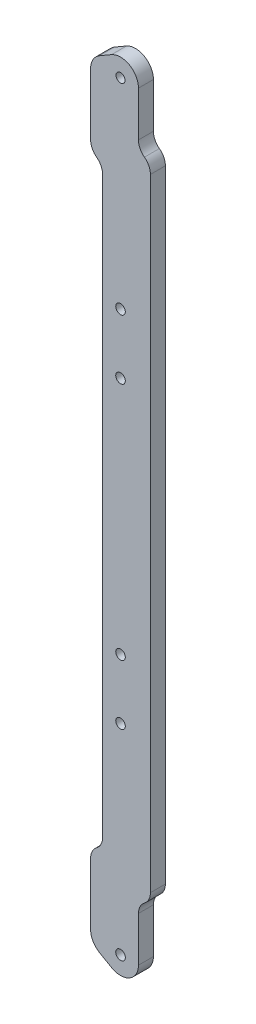
SolidWorks part; units mm, degrees
material "Thornel Mat VMA"
ref_plane "前视基准面" through (0, 0, 0) normal (0, 0, 1) x (1, 0, 0)
ref_plane "上视基准面" through (0, 0, 0) normal (0, 1, 0) x (1, 0, 0)
ref_plane "右视基准面" through (0, 0, 0) normal (1, 0, 0) x (0, 0, -1)
sketch "草图2" plane through (0, 0, 0) normal (0, 0, 1) x (1, 0, 0)
  line L1 (0, -43.1089) -> (-18, -43.1089)
  line L2 (0, -43.1089) -> (0, -133.1089)
  line L3 (0, -133.1089) -> (-18, -133.1089)
  line L4 (-18, -43.1089) -> (-18, -133.1089)
  circle A0 centre (-10, -125.1089) radius 1.6
  dimension "D1" = 18
  dimension "D2" = 8
  dimension "D3" = 3.2
  dimension "D4" = 82
  dimension "D5" = 8
extrude "凸台-拉伸1" add sketch "草图2" along normal blind 5
sketch "草图3" plane through (0, 0, 5) normal (0, 0, 1) x (1, 0, 0)
  line L0 (0, 1.8911) -> (-44.6895, 1.8911) construction
  line L1 (-18, 136.8911) -> (0, 136.8911)
  line L2 (-18, 46.8911) -> (-18, 136.8911)
  line L4 (0, -133.1089) -> (0, -43.1089)
  line L5 (0, -43.1089) -> (-18, -43.1089)
  line L6 (-18, -43.1089) -> (-18, -133.1089)
  line L7 (-18, -133.1089) -> (0, -133.1089)
  line L9 (0, -43.1089) -> (-18, -43.1089)
  line L12 (0, 136.8911) -> (0, 46.8911)
  line L15 (-18, 46.8911) -> (-18, -43.1089)
  line L16 (-18, -43.1089) -> (0, -43.1089)
  line L17 (0, 46.8911) -> (0, -43.1089)
  circle A1 centre (-10, 128.8911) radius 1.5
  line M11 (0, -43.1089) -> (-18, -43.1089)
  dimension "D3" = 8
  dimension "D4" = 10
  dimension "D5" = 127
  dimension "D2" = 45
  dimension "D1" = 0
extrude "凸台-拉伸2" add sketch "草图3" against normal blind 5 contours L0 L17 L12 L1 L2 L15 A1 | L17 L0 L15 M11 region at (-9, -20.6089, 5) region at (-8.9971, 69.2175, 5)
sketch "草图4" plane through (0, 0, 5) normal (0, 0, 1) x (1, 0, 0)
  circle A0 centre (-10, -58.1089) radius 1.6
  circle A1 centre (-10, -38.1089) radius 1.6
  circle A2 centre (-10, 41.8911) radius 1.6
  circle A3 centre (-10, 61.8911) radius 1.6
extrude "切除-拉伸1" cut sketch "草图4" against normal blind 5
sketch "草图5" plane through (0, 0, 5) normal (0, 0, 1) x (1, 0, 0)
  line L0 (-4, -125.1089) -> (-4, -110.1089)
  line L1 (0, -133.1089) -> (0, 136.8911) construction
  line L2 (-16, -125.1089) -> (-16, 128.8911)
  line L4 (0, 1.8911) -> (-11.675, 1.8911) construction
  line L5 (-16, 128.8911) -> (-16, -125.1089)
  line L6 (-4, 128.8911) -> (-4, 113.8911)
  line L7 (0, -102.1089) -> (0, -133.1089)
  line L8 (0, -133.1089) -> (-18, -133.1089)
  line L9 (-18, -133.1089) -> (-18, 136.8911)
  line L10 (-18, 136.8911) -> (0, 136.8911)
  line L11 (0, 136.8911) -> (0, 105.8911)
  circle A0 centre (-10, -125.1089) radius 6
  arc A1 (-4, -110.1089) -> (-2, -106.1089) centre (1, -110.1089) cw
  arc A2 (-2, -106.1089) -> (0, -102.1089) centre (-5, -102.1089) ccw
  arc A3 (-2, 109.8911) -> (0, 105.8911) centre (-5, 105.8911) cw
  arc A4 (-4, 113.8911) -> (-2, 109.8911) centre (1, 113.8911) ccw
  circle A5 centre (-10, 128.8911) radius 6
  line M7 (0, -133.1089) -> (0, 136.8911)
  line M8 (0, 136.8911) -> (-18, 136.8911)
  line M9 (-18, 136.8911) -> (-18, -133.1089)
  line M10 (-18, -133.1089) -> (0, -133.1089)
  dimension "D1" = 12
  dimension "D2" = 5
  dimension "D3" = 5
  dimension "D5" = 127
  dimension "D4" = 15
extrude "切除-拉伸2" cut sketch "草图5" against normal blind 5 and the other way through all contours L2 A5 L6 A4 A3 A2 A1 L0 A0 M7 M8 M9 M10 region at (-1.294, -117.6089, 5)
sketch "草图8" plane through (0, 0, 5) normal (0, 0, 1) x (1, 0, 0)
  line L0 (0, 1.8911) -> (-34.5992, 1.8911) construction
  line L1 (0, -102.1089) -> (0, 105.8911) construction
  line L2 (-13, 134.0873) -> (-17, 131.7779)
  line L3 (-20, 126.5817) -> (-20, 105.8911)
  line L4 (-18, 101.8911) -> (-16, 100.3911)
  line L5 (-16, -125.1089) -> (-16, 128.8911) construction
  line L6 (-16, 100.3911) -> (-16, 128.8911)
  line L7 (-2, 109.8911) -> (-8.2265, 114.561) construction
  line L8 (-4, 128.8911) -> (-4, 113.8911) construction
  line L9 (-2, -106.1089) -> (-8.2265, -110.7787) construction
  line L10 (-16, -96.6089) -> (-16, -125.1089)
  line L11 (-18, -98.1089) -> (-16, -96.6089)
  line L12 (-20, -122.7995) -> (-20, -102.1089)
  line L13 (-13, -130.305) -> (-17, -127.9956)
  arc A0 (-4, 128.8911) -> (-16, 128.8911) centre (-10, 128.8911) ccw construction
  arc A1 (-13, 134.0873) -> (-16, 128.8911) centre (-10, 128.8911) ccw
  arc A2 (-17, 131.7779) -> (-20, 126.5817) centre (-14, 126.5817) ccw
  arc A3 (-20, 105.8911) -> (-18, 101.8911) centre (-15, 105.8911) ccw
  arc A4 (0, 105.8911) -> (-2, 109.8911) centre (-5, 105.8911) ccw construction
  arc A5 (-20, -102.1089) -> (-18, -98.1089) centre (-15, -102.1089) cw
  arc A6 (-17, -127.9956) -> (-20, -122.7995) centre (-14, -122.7995) cw
  arc A7 (-13, -130.305) -> (-16, -125.1089) centre (-10, -125.1089) cw
  dimension "D1" = 6
  dimension "D2" = 5
  dimension "D3" = 16
  dimension "D4" = 16
  dimension "D5" = 60
extrude "凸台-拉伸3" add sketch "草图8" against normal up to vertex (5 mm away) up to point (-16, -125.1089, 0)
fillet "圆角1" radius 5 2 edges at (-16, 100.3911, 2.5) (-16, -96.6089, 2.5)
